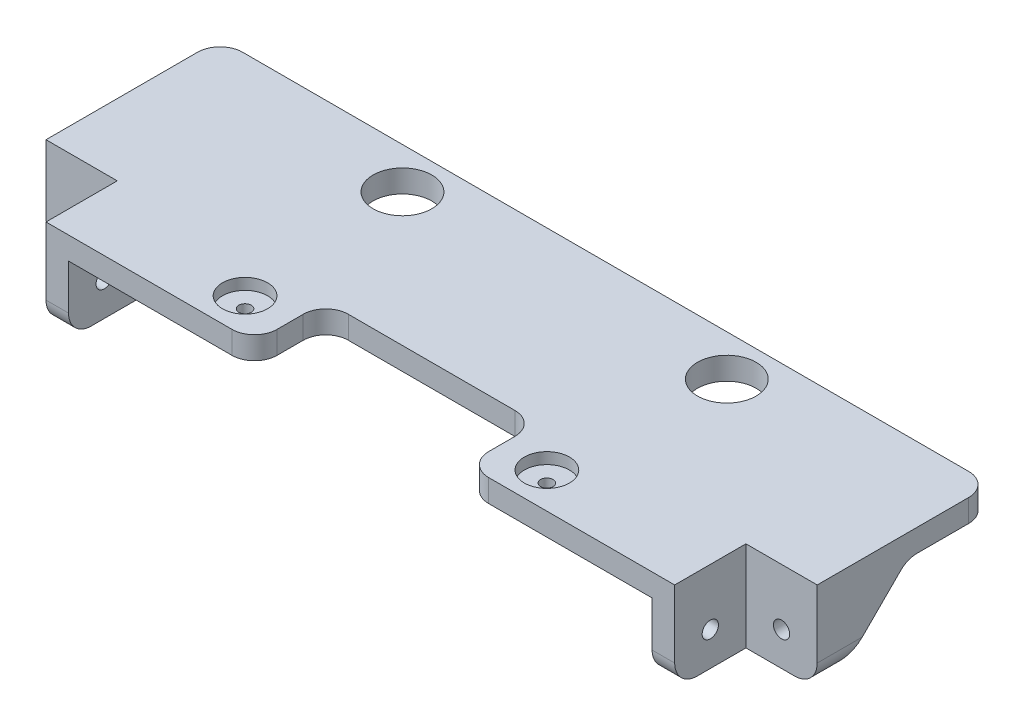
SolidWorks part; units mm, degrees
ref_plane "Front" through (0, 0, 0) normal (0, 0, 1) x (1, 0, 0)
ref_plane "Top" through (0, 0, 0) normal (0, 1, 0) x (1, 0, 0)
ref_plane "Right" through (0, 0, 0) normal (1, 0, 0) x (0, 0, -1)
sketch "Sketch1" plane through (0, 0, 0) normal (0, 1, 0) x (1, 0, 0)
  line L1 (-108.585, -24.511) -> (108.585, -24.511)
  line L2 (-108.585, -24.511) -> (-108.585, 24.511)
  line L3 (-108.585, 24.511) -> (108.585, 24.511)
  line L4 (108.585, -24.511) -> (108.585, 24.511)
  line L5 (-108.585, -24.511) -> (108.585, 24.511) construction
  line L6 (-108.585, 24.511) -> (108.585, -24.511) construction
  point P0 (0, 0)
  dimension "D1" = 49.022
  dimension "D2" = 217.17
extrude "Boss-Extrude1" add sketch "Sketch1" along normal blind 6.35
sketch "Sketch5" plane through (0, 0, 24.511) normal (0, 0, 1) x (1, 0, 0)
  line L1 (-108.585, 6.35) -> (-88.519, 6.35)
  line L2 (-108.585, 6.35) -> (-108.585, -19.05)
  line L3 (-108.585, -19.05) -> (-88.519, -19.05)
  line L4 (-88.519, 6.35) -> (-88.519, -19.05)
  line L5 (108.585, 6.35) -> (88.519, 6.35)
  line L6 (108.585, 6.35) -> (108.585, -19.05)
  line L7 (108.585, -19.05) -> (88.519, -19.05)
  line L8 (88.519, 6.35) -> (88.519, -19.05)
  dimension "D1" = 25.4
  dimension "D2" = 20.066
extrude "Boss-Extrude3" add sketch "Sketch5" against normal blind 6.35
sketch "Sketch6" plane through (0, 0, 0) normal (0, -1, 0) x (-1, 0, 0)
  line L0 (0, 0) -> (0, -50000) construction
  line L1 (42.5, -34.544) -> (-42.5, -34.544) construction
  line L2 (88.519, -24.511) -> (-88.519, -24.511) construction
  line L3 (55.2, -44.577) -> (29.8, -44.577)
  line L4 (55.2, -44.577) -> (55.2, -24.511)
  line L5 (55.2, -24.511) -> (29.8, -24.511)
  line L6 (29.8, -44.577) -> (29.8, -24.511)
  line L7 (55.2, -44.577) -> (29.8, -24.511) construction
  line L8 (55.2, -24.511) -> (29.8, -44.577) construction
  line L10 (-29.8, -44.577) -> (-55.2, -44.577)
  line L11 (-29.8, -44.577) -> (-29.8, -24.511)
  line L12 (-29.8, -24.511) -> (-55.2, -24.511)
  line L13 (-55.2, -44.577) -> (-55.2, -24.511)
  line L14 (-29.8, -44.577) -> (-55.2, -24.511) construction
  line L15 (-29.8, -24.511) -> (-55.2, -44.577) construction
  point P6 (0, -34.544)
  dimension "D1" = 85
  dimension "D2" = 20.066
  dimension "D3" = 25.4
extrude "Boss-Extrude4" add sketch "Sketch6" against normal up to surface (6.35 mm away) up to face at (0, 6.35, 0)
sketch "Sketch7" plane through (0, 0, 0) normal (0, -1, 0) x (1, 0, 0)
  line L0 (55.2, 34.544) -> (29.8, 34.544) construction
  line L1 (55.2, 24.511) -> (55.2, 44.577) construction
  line L2 (29.8, 44.577) -> (29.8, 24.511) construction
  line L3 (-29.8, 34.544) -> (-55.2, 34.544) construction
  line L4 (-29.8, 24.511) -> (-29.8, 44.577) construction
  line L5 (-55.2, 44.577) -> (-55.2, 24.511) construction
  circle A0 centre (-42.5, 34.544) radius 1.75
  circle A1 centre (42.5, 34.544) radius 1.75
  dimension "D1" = 3.5
extrude "Cut-Extrude1" cut sketch "Sketch7" against normal through all
sketch "Sketch9" plane through (0, 0, 18.161) normal (0, 0, -1) x (-1, 0, 0)
  line L0 (108.585, -9.525) -> (88.519, -9.525) construction
  line L1 (108.585, 0) -> (108.585, -19.05) construction
  line L2 (88.519, -19.05) -> (88.519, 0) construction
  line L3 (-88.519, -9.525) -> (-108.585, -9.525) construction
  line L4 (-88.519, 0) -> (-88.519, -19.05) construction
  line L5 (-108.585, -19.05) -> (-108.585, 0) construction
  circle A0 centre (98.552, -9.525) radius 2.286
  circle A1 centre (-98.552, -9.525) radius 2.286
  dimension "D1" = 4.572
extrude "Cut-Extrude2" cut sketch "Sketch9" against normal through all
sketch "Sketch14" plane through (-108.585, 0, 0) normal (-1, 0, 0) x (0, 0, 1)
  line L5 (18.161, 0) -> (18.161, -19.05)
  line L6 (-24.511, 6.35) -> (-24.511, 0)
  line L7 (24.511, 6.35) -> (-24.511, 6.35)
  line L8 (24.511, -19.05) -> (24.511, 6.35)
  line L9 (18.161, -19.05) -> (24.511, -19.05)
  line L11 (-24.511, 6.35) -> (-24.511, 0)
  line L12 (24.511, 6.35) -> (-24.511, 6.35)
  line L13 (24.511, -19.05) -> (24.511, 6.35)
  line L14 (18.161, -19.05) -> (24.511, -19.05)
  line L16 (18.161, 0) -> (18.161, -19.05)
  line L17 (-24.511, 0) -> (18.161, 0)
  line L18 (-24.511, 0) -> (18.161, 0)
  dimension "D1" = 0
extrude "Boss-Extrude8" add sketch "Sketch14" against normal blind 3.175
sketch "Sketch15" plane through (0, 0, 0) normal (0, -1, 0) x (1, 0, 0)
  circle A0 centre (42.5, 34.544) radius 6.35
  circle A1 centre (-42.5, 34.544) radius 6.35
  circle M3 centre (-42.5, 34.544) radius 1.75
  circle M4 centre (42.5, 34.544) radius 1.75
  dimension "D1" = 12.7
extrude "Boss-Extrude9" add sketch "Sketch15" along normal blind 1.2 contours A0 M4 | A1 M3 region at (36.3296, 0, 34.544) region at (-48.6704, 0, 34.544)
sketch "Sketch16" plane through (0, 6.35, 0) normal (0, 1, 0) x (1, 0, 0)
  circle A0 centre (42.5, -34.544) radius 6.35
  circle A1 centre (-42.5, -34.544) radius 6.35
  dimension "D1" = 12.7
extrude "Cut-Extrude4" cut sketch "Sketch16" against normal blind 3.175
sketch "Sketch17" plane through (0, 0, 0) normal (0, -1, 0) x (1, 0, 0)
  line L1 (-42.5, 34.544) -> (42.5, 34.544) construction
  line L2 (-42.5, 34.544) -> (-42.5, -12.956) construction
  line L3 (-42.5, -12.956) -> (42.5, -12.956) construction
  line L4 (42.5, 34.544) -> (42.5, -12.956) construction
  circle A2 centre (-45.675, -12.956) radius 8.255
  circle A3 centre (45.675, -12.956) radius 8.255
  point P10 (0, 0)
  point P11 (0, 0)
  point P12 (0, 0)
  point P13 (0, 0)
  dimension "D2" = 16.51
  dimension "D1" = 47.5
  dimension "D3" = 3.175
  dimension "D4" = 3.175
extrude "Cut-Extrude5" cut sketch "Sketch17" against normal through all
sketch "Sketch18" plane through (0, 0, 0) normal (0, -1, 0) x (1, 0, 0)
  line L1 (88.519, 24.511) -> (55.2, 24.511)
  line L2 (88.519, 24.511) -> (88.519, 44.577)
  line L3 (88.519, 44.577) -> (55.2, 44.577)
  line L4 (55.2, 24.511) -> (55.2, 44.577)
  line L5 (-55.2, 44.577) -> (-88.519, 44.577)
  line L6 (-55.2, 44.577) -> (-55.2, 24.511)
  line L7 (-55.2, 24.511) -> (-88.519, 24.511)
  line L8 (-88.519, 44.577) -> (-88.519, 24.511)
extrude "Boss-Extrude10" add sketch "Sketch18" against normal up to surface (6.35 mm away) up to face at (-45.675, 6.35, -21.211)
sketch "Sketch19" plane through (88.519, 0, 0) normal (-1, 0, 0) x (0, 0, 1)
  line L0 (24.511, -19.05) -> (24.511, 0) construction
  line L1 (24.511, -19.05) -> (44.577, -19.05)
  line L3 (24.511, 0) -> (44.577, 0)
  line L4 (24.511, -19.05) -> (24.511, 0)
  line L5 (24.511, 0) -> (18.161, 0)
  line L6 (18.161, 0) -> (18.161, -19.05)
  line L7 (18.161, -19.05) -> (24.511, -19.05)
  line L9 (24.511, 0) -> (18.161, 0)
  line L11 (18.161, -19.05) -> (24.511, -19.05)
  line L12 (44.577, -19.05) -> (44.577, 0)
  line L13 (24.511, -9.525) -> (44.577, -9.525) construction
  line L19 (18.161, 0) -> (18.161, -19.05)
  circle A0 centre (34.544, -9.525) radius 2.286
  dimension "D2" = 4.572
  dimension "D1" = 0
extrude "Boss-Extrude11" add sketch "Sketch19" along normal blind 6.35
sketch "Sketch20" plane through (-88.519, 0, 0) normal (1, 0, 0) x (0, 0, -1)
  line L4 (-44.577, -19.05) -> (-18.161, -19.05)
  line L5 (-44.577, 0) -> (-44.577, -19.05)
  line L6 (-18.161, 0) -> (-44.577, 0)
  line L7 (-18.161, -19.05) -> (-18.161, 0)
  line L8 (-44.577, -19.05) -> (-18.161, -19.05)
  line L9 (-44.577, 0) -> (-44.577, -19.05)
  line L10 (-18.161, 0) -> (-44.577, 0)
  line L11 (-18.161, -19.05) -> (-18.161, 0)
  circle A0 centre (-34.544, -9.525) radius 2.286 construction
  circle A1 centre (-34.544, -9.525) radius 2.286
  dimension "D1" = 0
extrude "Boss-Extrude12" add sketch "Sketch20" along normal blind 6.35
sketch "Sketch21" plane through (-108.585, 0, 0) normal (-1, 0, 0) x (0, 0, 1)
  line L0 (18.161, -19.05) -> (-0.889, 0)
  line L1 (-24.511, 0) -> (18.161, 0) construction
  line L2 (-0.889, 0) -> (18.161, 0)
  line L3 (18.161, 0) -> (18.161, -19.05)
extrude "Boss-Extrude13" add sketch "Sketch21" against normal blind 3.175
sketch "Sketch22" plane through (108.585, 0, 0) normal (1, 0, 0) x (0, 0, -1)
  line L3 (-18.161, 0) -> (-18.161, -19.05)
  line L4 (-18.161, -19.05) -> (0.889, 0)
  line L5 (0.889, 0) -> (-18.161, 0)
  line L6 (-18.161, 0) -> (-18.161, -19.05)
  line L7 (-18.161, -19.05) -> (0.889, 0)
  line L8 (0.889, 0) -> (-18.161, 0)
  dimension "D1" = 0
extrude "Boss-Extrude14" add sketch "Sketch22" against normal blind 3.175
sketch "Sketch23" plane through (-82.169, 0, 0) normal (1, 0, 0) x (0, 0, -1)
  line L3 (-18.161, 0) -> (-18.161, -19.05)
  line L4 (-18.161, -19.05) -> (0.889, 0)
  line L5 (0.889, 0) -> (-18.161, 0)
  line L6 (-18.161, 0) -> (-18.161, -19.05)
  line L7 (-18.161, -19.05) -> (0.889, 0)
  line L8 (0.889, 0) -> (-18.161, 0)
  dimension "D1" = 0
extrude "Boss-Extrude15" add sketch "Sketch23" against normal blind 6.35
sketch "Sketch24" plane through (82.169, 0, 0) normal (-1, 0, 0) x (0, 0, 1)
  line L3 (18.161, 0) -> (-0.889, 0)
  line L4 (-0.889, 0) -> (18.161, -19.05)
  line L5 (18.161, -19.05) -> (18.161, 0)
  line L6 (18.161, 0) -> (-0.889, 0)
  line L7 (-0.889, 0) -> (18.161, -19.05)
  line L8 (18.161, -19.05) -> (18.161, 0)
  dimension "D1" = 0
extrude "Boss-Extrude16" add sketch "Sketch24" against normal blind 6.35
fillet "Fillet2" radius 6.35 6 edges at (-29.8, 3.175, 44.577) (-29.8, 3.175, 24.511) (29.8, 3.175, 24.511) (29.8, 3.175, 44.577) (-85.344, -19.05, 44.577) (85.344, -19.05, 44.577)
fillet "Fillet3" radius 6.35 8 edges at (108.585, -19.05, 21.336) (-108.585, -19.05, 21.336) (106.9975, 0, -0.889) (85.344, 0, -0.889) (108.585, 3.175, -24.511) (-108.585, 3.175, -24.511) (-85.344, 0, -0.889) (-106.9975, 0, -0.889)
